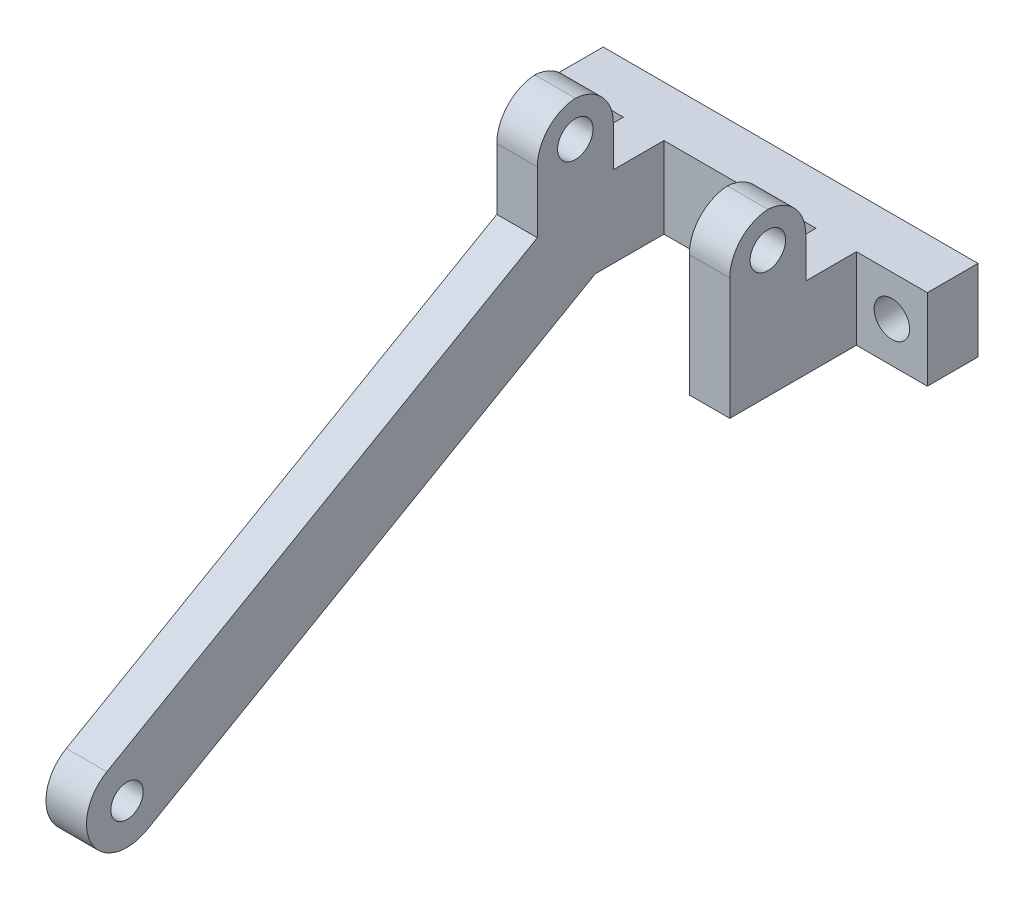
SolidWorks part; units mm, degrees
ref_plane "Front Plane" through (0, 0, 0) normal (0, 0, 1) x (1, 0, 0)
ref_plane "Top Plane" through (0, 0, 0) normal (0, 1, 0) x (1, 0, 0)
ref_plane "Right Plane" through (0, 0, 0) normal (1, 0, 0) x (0, 0, -1)
sketch "Sketch1" plane through (0, 0, 0) normal (0, 0, 1) x (1, 0, 0)
  line L0 (15, 0) -> (-15, 0) construction
  line L1 (-18.5, 4) -> (18.5, 4)
  line L2 (-18.5, 4) -> (-18.5, -4)
  line L3 (-18.5, -4) -> (18.5, -4)
  line L4 (18.5, 4) -> (18.5, -4)
  line L5 (-18.5, 4) -> (18.5, -4) construction
  line L6 (-18.5, -4) -> (18.5, 4) construction
  line L7 (0, -4) -> (0, 4) construction
  circle A0 centre (-15, 0) radius 1.75
  circle A1 centre (15, 0) radius 1.75
  point P0 (0, 0)
  point P12 (0, 0)
  dimension "D3" = 3.5
  dimension "D1" = 37
  dimension "D2" = 8
  dimension "D4" = 15
extrude "Boss-Extrude1" add sketch "Sketch1" along normal blind 5
sketch "Sketch2" plane through (0, 0, 5) normal (0, 0, 1) x (1, 0, 0)
  line L0 (0, 4) -> (0, -4) construction
  line L1 (18.5, 4) -> (-18.5, 4) construction
  line L2 (-18.5, -4) -> (18.5, -4) construction
  line L3 (11.5, -4) -> (7.5, 4) construction
  line L4 (-11.5, 4) -> (-7.5, 4)
  line L5 (-11.5, 4) -> (-11.5, -4)
  line L6 (-11.5, -4) -> (-7.5, -4)
  line L7 (-7.5, 4) -> (-7.5, -4)
  line L8 (-11.5, 4) -> (-7.5, -4) construction
  line L9 (-11.5, -4) -> (-7.5, 4) construction
  line L10 (11.5, 4) -> (7.5, -4) construction
  line L11 (7.5, 4) -> (7.5, -4)
  line L12 (11.5, -4) -> (7.5, -4)
  line L13 (11.5, 4) -> (11.5, -4)
  line L14 (11.5, 4) -> (7.5, 4)
  point P6 (-9.5, 0)
  point P15 (9.5, 0)
  dimension "D1" = 7.5
  dimension "D2" = 4
extrude "Boss-Extrude2" add sketch "Sketch2" along normal blind 12.5
sketch "Sketch4" plane through (0, 4, 0) normal (0, 1, 0) x (1, 0, 0)
  line L0 (-7.5, -17.5) -> (-7.5, -5) construction
  line L1 (-11.5, -17.5) -> (-7.5, -17.5)
  line L2 (-11.5, -17.5) -> (-11.5, -10)
  line L3 (-11.5, -10) -> (-7.5, -10)
  line L4 (-7.5, -17.5) -> (-7.5, -10)
  line L5 (0, 0) -> (0, -5) construction
  line L6 (7.5, -5) -> (-7.5, -5) construction
  line L7 (7.5, -17.5) -> (7.5, -10)
  line L8 (11.5, -10) -> (7.5, -10)
  line L9 (11.5, -17.5) -> (11.5, -10)
  line L10 (11.5, -17.5) -> (7.5, -17.5)
  dimension "D1" = 7.5
extrude "Boss-Extrude3" add sketch "Sketch4" along normal blind 8
sketch "Sketch3" plane through (-11.5, 0, 0) normal (-1, 0, 0) x (0, 0, 1)
  line L0 (10, 8.5) -> (17.5, 8.5) construction
  line L4 (10, 12) -> (10, 4) construction
  line L5 (17.5, 12) -> (17.5, -4) construction
  line L6 (13.75, 8.5) -> (13.75, 12) construction
  line L7 (10, 12) -> (17.5, 12) construction
  circle A0 centre (13.75, 8.5) radius 1.75
  dimension "D1" = 3.5
  dimension "D2" = 8.5
extrude "Cut-Extrude1" cut sketch "Sketch3" against normal through all
fillet "Fillet1" radius 4 4 edges at (-9.5, 12, 10) (9.5, 12, 10) (9.5, 12, 17.5) (-9.5, 12, 17.5)
sketch "Sketch5" plane through (-7.5, 0, 0) normal (1, 0, 0) x (0, 0, -1)
  line L0 (-10, 8) -> (-10, 4) construction
  line L1 (-10, 6.5) -> (-13, 6.5)
  line L2 (-10, 6.5) -> (-10, 1.5)
  line L3 (-10, 1.5) -> (-13, 1.5)
  line L4 (-13, 6.5) -> (-13, 1.5)
  line L5 (-10, 4) -> (-5, 4) construction
  dimension "D1" = 3
  dimension "D2" = 5
  dimension "D3" = 2.5
extrude "Boss-Extrude4" [suppressed] add sketch "Sketch5" along normal up to next
sketch "Sketch6" plane through (-11.5, 0, 0) normal (-1, 0, 0) x (0, 0, 1)
  line L0 (56.0113, -29.4012) -> (11.7824, -4)
  line L1 (17.5, -4) -> (5, -4) construction
  line L2 (11.7824, -4) -> (17.5, 1.9418)
  line L3 (13.75, 8.5) -> (58.0033, -25.9326) construction
  line L4 (17.5, 1.9418) -> (59.9954, -22.4639)
  line L5 (59.9954, -22.4639) -> (56.0113, -29.4012) construction
  line L6 (13.75, 8.5) -> (13.75, -4) construction
  line L7 (17.5, 8) -> (17.5, -4) construction
  circle A0 centre (58.0033, -25.9326) radius 1.6
  arc A1 (56.0113, -29.4012) -> (59.9954, -22.4639) centre (58.0033, -25.9326) ccw
  dimension "D1" = 3.2
  dimension "D2" = 8
  dimension "D3" = 52.114
  dimension "D4" = 56.071
  dimension "D5" = 1.9676
extrude "Boss-Extrude5" add sketch "Sketch6" against normal up to surface (4 mm away) up to face at (-7.5, 6.75, 13.75)
equation "\"X-ROD-SPACING\"=45"
equation "\"Y-ROD-SPACING\"=75"
equation "\"Z-ROD-SPACING\"=17.5"
equation "\"Y-BED-OFFSET\"=2"
equation "\"Y-BED-ROD-INSET\"=3.5"
equation "\"Y-BED-SCREW-SPACING\"=209"
equation "\"Y-BED-SCREW-CUTOUT-SLOT-HEIGHT\"=2"
equation "\"T-SLOT-NUT-FILLET-RADIUS\"=0.5"
equation "\"T-SLOT-SCREW-SHAFT-RADIUS\"=1.55"
equation "\"T-SLOT-SCREW-SHAFT-CUTOUT-LENGTH\"=11"
equation "\"T-SLOT-NUT-DEPTH\"=3.5"
equation "\"T-SLOT-NUT-WIDTH\"=2.85"
equation "\"T-SLOT-NUT-END-DISTANCE\"=8"
equation "\"ACRYLIC-THICKNESS\"=10"
equation "\"ACRYLIC-THICKNESS2\"=4.5"
equation "\"ACRYLIC-TAB-CUTOUT-SIZE\"=\"ACRYLIC-THICKNESS\"+\"ACRYLIC-TAB-TOLERANCE\"*2"
equation "\"ACRYLIC-TAB-TOLERANCE\"=-.05"
equation "\"ACRYLIC-TAB-WIDTH\"=\"ACRYLIC-THICKNESS\""
equation "\"ACRYLIC-M3-HOLE\"=2.9"
equation "\"SMOOTHROD-CAP-SCREW-DISTANCE\"=20"
equation "\"FRAME-WIDTH-INNER\"=370"
equation "\"NEMA17-HOLE-SPACING\"=31"
equation "\"NEMA17-CENTRAL-CUTOUT\"=22.5"
equation "\"Z-BRACKET-REACH\"=55"
equation "\"Z-ROD-INSET\"=13.5"
equation "\"TOP-BRACKET-SPACING\"=40"
equation "\"SMOOTHROD-X-LENGTH\"=350"
equation "\"SMOOTHROD-Y-LENGTH\"=350"
equation "\"SMOOTHROD-Z-LENGTH\"=350"
equation "\"SMOOTHROD-TIGHTENING-HEADROOM\"=.25"
equation "\"LEADSCREW-Z-LENGTH\"=300"
equation "\"SCREW-LENGTH-FRAME\"=\"ACRYLIC-THICKNESS\" + 10"
equation "\"SCREW-LENGTH-MOTOR\"=\"ACRYLIC-THICKNESS\" + 5"
equation "\"SCREW-LENGTH-EXTRUDER\"=28"
equation "\"SCREW-HEAD-RADIUS\"=6"
equation "\"PRINTED-X-SMOOTHROD-DIAMETER\"=8.8"
equation "\"PRINTED-X-SMOOTHROD-CUTOUT\"=10"
equation "\"PRINTED-X-BASE-HEIGHT\"=10"
equation "\"PRINTED-LM8UU-CUTOUT-SIZE\"=15.5"
equation "\"PRINTED-LM8UU-CUTOUT-LENGTH\"=24.5"
equation "\"PRINTED-X-IDLER-HEIGHT\"=16"
equation "\"PSU-MOUNTING-WIDTH\"=95"
equation "\"PSU-MOUNTING-HEIGHT\"=177"
equation "\"Y-BELT-TO-ROD-DISTANCE\"=20"
equation "\"SPOOL-HOLDER-ROD-SPACING\"=150"
equation "\"ACRYLIC-X-CARRIAGE-WIDTH\"=55"
equation "\"ACRYLIC-X-CARRIAGE-HEIGHT\"=75"
equation "\"ACRYLIC-X-CARRIAGE-LM8UU-CUTOUT-WIDTH\"=24.25"
equation "\"ACRYLIC-X-CARRIAGE-LM8UU-CUTOUT-HEIGHT\"=11.0"
equation "\"ACRYLIC-X-CARRIAGE-SCREW-SPACING-X\"=15"
equation "\"ACRYLIC-X-CARRIAGE-SCREW-SPACING-Y\"=33"
equation "\"ACRYLIC-X-CARRIAGE-CENTER-TAB-SPACING\"=14"
equation "\"ACRYLIC-X-CARRIAGE-EXTRUDER-OFFSET\"=26"
equation "\"ACRYLIC-X-CARRIAGE-EXTRUDER-ANGLE\"=90"
equation "\"ACRYLIC-X-CARRIAGE-EXTRUDER-SHELF-DEPTH\"=\"ACRYLIC-X-CARRIAGE-EXTRUDER-OFFSET\" + 28"
equation "\"ACRYLIC-X-CARRIAGE-EXTRUDER-BRACE-SPACING\"=23"
equation "\"ACRYLIC-X-CARRIAGE-EXTRUDER-BRACE-TAB-OFFSET\"=20"
equation "\"ACRYLIC-X-CARRIAGE-EXTRUDER-BRACE-HEIGHT\"=35"
equation "\"ACRYLIC-X-CARRIAGE-EXTRUDER-BRACE-SCREW-SPACING\"=22"
equation "\"ACRYLIC-X-CARRIAGE-DUAL-WIDTH-MULTIPLIER\"=1.65"
equation "\"ACRYLIC-X-CARRIAGE-DUAL-HOTEND-SPACING\"=42"
equation "\"ACRYLIC-X-CARRIAGE-DUAL-WIDTH\"=75"
equation "\"ACRYLIC-X-CARRIAGE-DUAL-HOTEND-SEPARATION\"=36"
equation "\"ACRYLIC-X-CARRIAGE-DUAL-MOUNT-PLATE-DEPTH\"=75"
equation "\"ACRYLIC-X-CARRIAGE-DUAL-MOUNT-BRACE-WIDTH\"=33"
equation "\"ACRYLIC-X-CARRIAGE-DUAL-MOUNT-SCREW-WIDTH\"=40"
equation "\"D3@Sketch1\"=3.5"
equation "\"PRINTED-M3-HOLE\"=3.5"
equation "\"BLOWER-FAN-WIDTH\"=15"
equation "\"D1@Sketch2\"=\"BLOWER-FAN-WIDTH\"/2"
